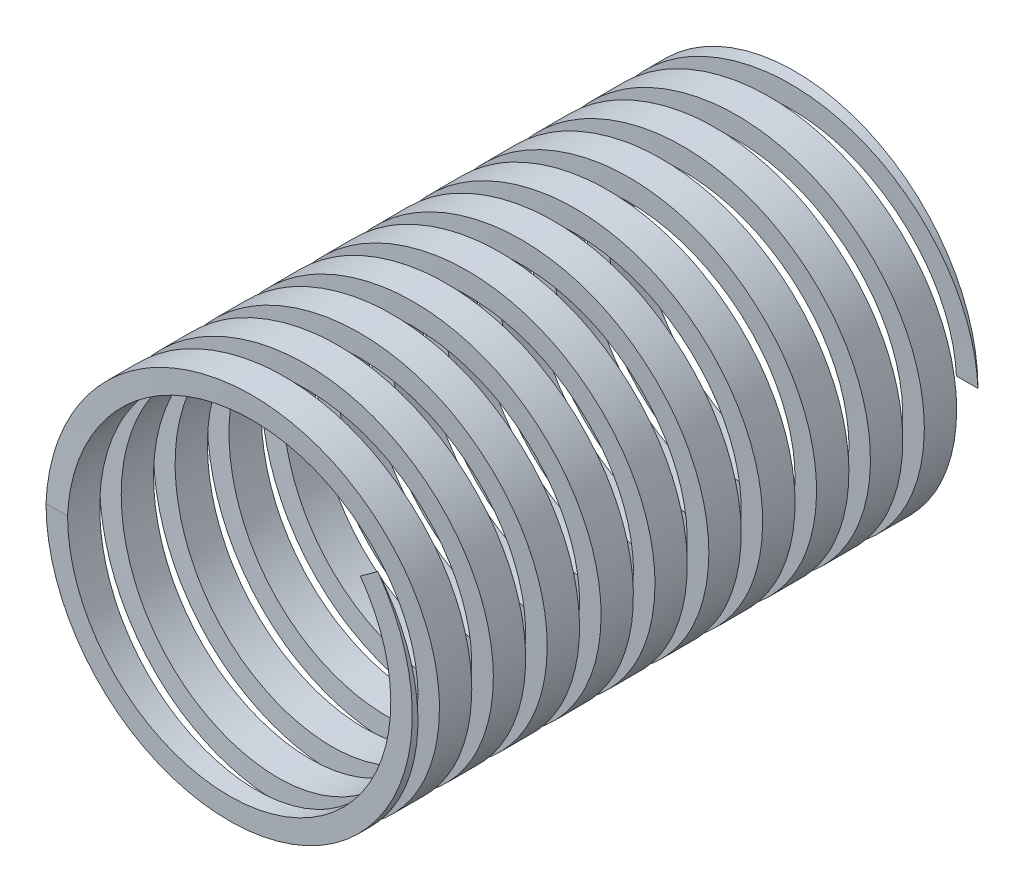
SolidWorks part; units mm, degrees
ref_plane "Přední rovina" through (0, 0, 0) normal (0, 0, 1) x (1, 0, 0)
ref_plane "Horní rovina" through (0, 0, 0) normal (0, 1, 0) x (1, 0, 0)
ref_plane "Pravá rovina" through (0, 0, 0) normal (1, 0, 0) x (0, 0, -1)
sketch "Skica1" plane through (0, 0, 0) normal (0, 0, 1) x (1, 0, 0)
  circle A0 centre (0, 0) radius 1.5
  circle A1 centre (0, 0) radius 1.7
  dimension "D1" = 3
  dimension "D2" = 0.2
extrude "Přidat vysunutím1" add sketch "Skica1" along normal blind 5.25
sketch "Skica3" plane through (0, 0, 0) normal (0, 0, -1) x (-1, 0, 0)
  circle A0 centre (0, 0) radius 1.7
curve "Šroubovice/spirála2" pitch 0.5 height 6.25 radius 1.7 centre (0, 0, 0) axis (0, 0, 1) start towards (1, 0, 0)
sketch "Skica4" plane through (0, 0, 0) normal (0, 1, 0) x (1, 0, 0)
  line L1 (1.7, 0) -> (1.45, 0)
  line L2 (1.7, 0) -> (1.7, -0.2)
  line L3 (1.7, -0.2) -> (1.45, -0.2)
  line L4 (1.45, 0) -> (1.45, -0.2)
  dimension "D1" = 0.2
  dimension "D2" = 0.25
sweep "Odebrat tažením po křivce1" cut profiles "Skica4" path "Šroubovice/spirála2" align with end faces yes
